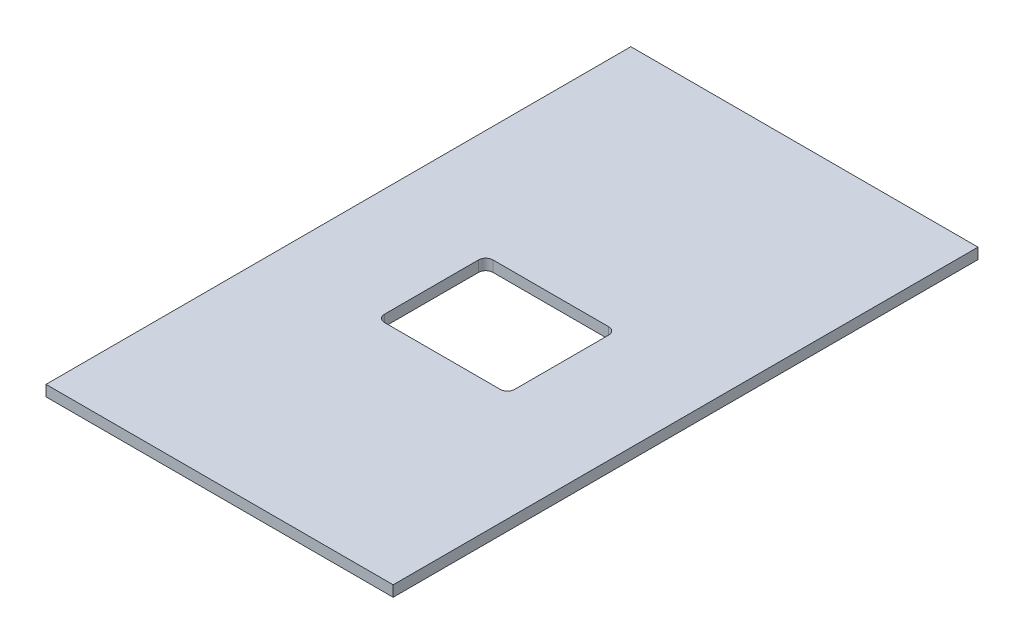
SolidWorks part; units mm, degrees
material "Balsa"
ref_plane "Front Plane" through (0, 0, 0) normal (0, 0, 1) x (1, 0, 0)
ref_plane "Top Plane" through (0, 0, 0) normal (0, 1, 0) x (1, 0, 0)
ref_plane "Right Plane" through (0, 0, 0) normal (1, 0, 0) x (0, 0, -1)
sketch "Sketch1" plane through (0, 0, 0) normal (0, 1, 0) x (1, 0, 0)
  line L0 (-152.4, 304.8) -> (152.4, 304.8) construction
  line L1 (152.4, 304.8) -> (152.4, -304.8) construction
  line L2 (0, 304.8) -> (0, 0) construction
  line L3 (0, 0) -> (152.4, 0) construction
  dimension "Width" = 304.8
  dimension "Length" = 609.6
sketch "Sketch2" plane through (0, 0, 0) normal (1, 0, 0) x (0, 0, -1)
  line L0 (304.8, 0) -> (304.8, -9.525) construction
  dimension "Thk" = 9.525
sketch "Sketch3" plane through (0, 0, 0) normal (0, 1, 0) x (1, 0, 0)
  line L1 (-152.4, 304.8) -> (152.4, 304.8)
  line L2 (-152.4, 304.8) -> (-152.4, -304.8)
  line L3 (-152.4, -304.8) -> (152.4, -304.8)
  line L4 (152.4, 304.8) -> (152.4, -304.8)
extrude "Boss-Extrude1" add sketch "Sketch3" against normal up to vertex (9.525 mm away) up to point (0, -9.525, -304.8)
sketch "Sketch4" plane through (0, 0, 0) normal (0, 1, 0) x (1, 0, 0)
  line L0 (152.4, -304.8) -> (152.4, 304.8) construction
  line L1 (-152.4, 304.8) -> (152.4, 304.8)
  line L2 (-152.4, 304.8) -> (-152.4, 208.661)
  line L3 (-152.4, 208.661) -> (152.4, 208.661)
  line L4 (152.4, 304.8) -> (152.4, 208.661)
  line L5 (-152.4, -304.8) -> (152.4, -304.8) construction
  dimension "D1" = 513.461
extrude "Cut-Extrude1" cut sketch "Sketch4" against normal blind 15.24 contours L2 L1 L4 L3
sketch "Sketch5" plane through (0, 0, 0) normal (0, 1, 0) x (1, 0, 0)
  line L1 (-50.8, -109.22) -> (50.8, -109.22)
  line L2 (-57.15, -102.87) -> (-57.15, -20.32)
  line L3 (-50.8, -13.97) -> (50.8, -13.97)
  line L4 (57.15, -102.87) -> (57.15, -20.32)
  line L5 (-57.15, -109.22) -> (57.15, -13.97) construction
  line L6 (-57.15, -13.97) -> (57.15, -109.22) construction
  arc A0 (-50.8, -109.22) -> (-57.15, -102.87) centre (-50.8, -102.87) cw
  arc A1 (50.8, -109.22) -> (57.15, -102.87) centre (50.8, -102.87) ccw
  arc A2 (50.8, -13.97) -> (57.15, -20.32) centre (50.8, -20.32) cw
  arc A3 (-57.15, -20.32) -> (-50.8, -13.97) centre (-50.8, -20.32) cw
  point P0 (0, -61.595)
  point P18 (0, 0)
  dimension "D4" = 6.35
  dimension "D1" = 95.25
  dimension "D2" = 61.595
  dimension "D3" = 114.3
extrude "Cut-Extrude2" cut sketch "Sketch5" against normal blind 12.7
